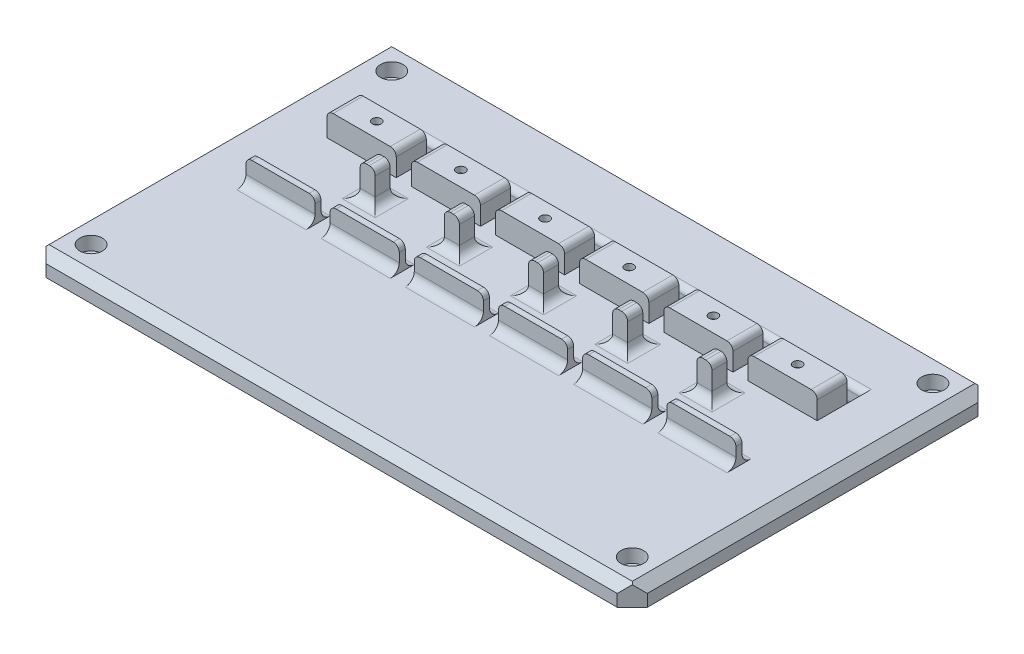
SolidWorks part; units mm, degrees
ref_plane "Front Plane" through (0, 0, 0) normal (0, 0, 1) x (1, 0, 0)
ref_plane "Top Plane" through (0, 0, 0) normal (0, 1, 0) x (1, 0, 0)
ref_plane "Right Plane" through (0, 0, 0) normal (1, 0, 0) x (0, 0, -1)
sketch "Sketch1" plane through (0, 0, 0) normal (0, 1, 0) x (1, 0, 0)
  line L1 (-111.1824, -29.2905) -> (88.8176, -29.2905)
  line L2 (-111.1824, -29.2905) -> (-111.1824, 90.7095)
  line L3 (-111.1824, 90.7095) -> (88.8176, 90.7095)
  line L4 (88.8176, -29.2905) -> (88.8176, 90.7095)
  dimension "D1" = 120
  dimension "D2" = 200
extrude "Boss-Extrude1" add sketch "Sketch1" along normal blind 7
chamfer "Chamfer1" distance 5 angle 45 4 edges at (88.8176, 3.5, 29.2905) (88.8176, 3.5, -90.7095) (-111.1824, 3.5, -90.7095) (-111.1824, 3.5, 29.2905)
sketch "Sketch14" plane through (0, 0, 0) normal (0, -1, 0) x (1, 0, 0)
  line L0 (-106.1824, 29.2905) -> (83.8176, 29.2905) construction
  line L1 (-111.1824, -85.7095) -> (-111.1824, 24.2905) construction
  line L2 (83.8176, -90.7095) -> (-106.1824, -90.7095) construction
  line L3 (88.8176, 24.2905) -> (88.8176, -85.7095) construction
  circle A0 centre (-101.1824, 19.2905) radius 1.5
  circle A1 centre (-101.1824, -80.7095) radius 1.5
  circle A2 centre (78.8176, 19.2905) radius 1.5
  circle A3 centre (78.8176, -80.7095) radius 1.5
  dimension "D1" = 3
  dimension "D4" = 3
  dimension "D5" = 3
  dimension "D8" = 3
  dimension "D2" = 10
  dimension "D3" = 10
  dimension "D6" = 10
  dimension "D7" = 10
extrude "Cut-Extrude13" cut sketch "Sketch14" against normal through all
sketch "Sketch16" plane through (0, 7, 0) normal (0, -1, 0) x (1, 0, 0)
  circle A0 centre (-101.1824, 19.2905) radius 3.75
  circle A1 centre (78.8176, 19.2905) radius 3.75
  circle A2 centre (-101.1824, -80.7095) radius 3.75
  circle A3 centre (78.8176, -80.7095) radius 3.75
  dimension "D1" = 7.5
  dimension "D2" = 7.5
  dimension "D3" = 7.5
  dimension "D4" = 7.5
extrude "Cut-Extrude14" cut sketch "Sketch16" along normal blind 4.5
sketch "Sketch17" plane through (0, 7, 0) normal (0, 1, 0) x (1, 0, 0)
  line L1 (-92.6824, 50.7095) -> (-69.6824, 50.7095)
  line L2 (-92.6824, 50.7095) -> (-92.6824, 60.7095)
  line L3 (-92.6824, 60.7095) -> (-69.6824, 60.7095)
  line L4 (-69.6824, 50.7095) -> (-69.6824, 60.7095)
  line L6 (83.8176, 90.7095) -> (-106.1824, 90.7095) construction
  line L7 (-64.6824, 60.7095) -> (-41.6824, 60.7095)
  line L8 (-64.6824, 60.7095) -> (-64.6824, 50.7095)
  line L9 (-64.6824, 50.7095) -> (-41.6824, 50.7095)
  line L10 (-41.6824, 60.7095) -> (-41.6824, 50.7095)
  line L11 (-36.6824, 60.7095) -> (-13.6824, 60.7095)
  line L12 (-36.6824, 60.7095) -> (-36.6824, 50.7095)
  line L13 (-36.6824, 50.7095) -> (-13.6824, 50.7095)
  line L14 (-13.6824, 60.7095) -> (-13.6824, 50.7095)
  line L15 (-8.6824, 60.7095) -> (14.3176, 60.7095)
  line L16 (-8.6824, 60.7095) -> (-8.6824, 50.7095)
  line L17 (-8.6824, 50.7095) -> (14.3176, 50.7095)
  line L18 (14.3176, 60.7095) -> (14.3176, 50.7095)
  line L19 (19.3176, 60.7095) -> (42.3176, 60.7095)
  line L20 (19.3176, 60.7095) -> (19.3176, 50.7095)
  line L21 (19.3176, 50.7095) -> (42.3176, 50.7095)
  line L22 (42.3176, 60.7095) -> (42.3176, 50.7095)
  line L23 (47.3176, 60.7095) -> (70.3176, 60.7095)
  line L24 (47.3176, 60.7095) -> (47.3176, 50.7095)
  line L25 (47.3176, 50.7095) -> (70.3176, 50.7095)
  line L26 (70.3176, 60.7095) -> (70.3176, 50.7095)
  line L27 (-92.6824, 25.7095) -> (-69.6824, 25.7095)
  line L28 (-92.6824, 25.7095) -> (-92.6824, 23.7095)
  line L29 (-92.6824, 23.7095) -> (-69.6824, 23.7095)
  line L30 (-69.6824, 25.7095) -> (-69.6824, 23.7095)
  line L31 (-111.1824, 85.7095) -> (-111.1824, -24.2905) construction
  line L34 (-64.6824, 25.7095) -> (-41.6824, 25.7095)
  line L35 (-64.6824, 25.7095) -> (-64.6824, 23.7095)
  line L36 (-64.6824, 23.7095) -> (-41.6824, 23.7095)
  line L37 (-41.6824, 25.7095) -> (-41.6824, 23.7095)
  line L38 (-36.6824, 25.7095) -> (-13.6824, 25.7095)
  line L39 (-36.6824, 25.7095) -> (-36.6824, 23.7095)
  line L40 (-36.6824, 23.7095) -> (-13.6824, 23.7095)
  line L41 (-13.6824, 25.7095) -> (-13.6824, 23.7095)
  line L42 (-8.6824, 25.7095) -> (14.3176, 25.7095)
  line L43 (-8.6824, 25.7095) -> (-8.6824, 23.7095)
  line L44 (-8.6824, 23.7095) -> (14.3176, 23.7095)
  line L45 (14.3176, 25.7095) -> (14.3176, 23.7095)
  line L46 (19.3176, 25.7095) -> (42.3176, 25.7095)
  line L47 (19.3176, 25.7095) -> (19.3176, 23.7095)
  line L48 (19.3176, 23.7095) -> (42.3176, 23.7095)
  line L49 (42.3176, 25.7095) -> (42.3176, 23.7095)
  line L50 (47.3176, 25.7095) -> (70.3176, 25.7095)
  line L51 (47.3176, 25.7095) -> (47.3176, 23.7095)
  line L52 (47.3176, 23.7095) -> (70.3176, 23.7095)
  line L53 (70.3176, 25.7095) -> (70.3176, 23.7095)
  point P6 (-92.6824, 55.7095)
  point P33 (-69.6824, 55.7095)
  dimension "D1" = 30
  dimension "D2" = 23
  dimension "D3" = 10
  dimension "D4" = 18.5
  dimension "D5" = 5
  dimension "D6" = 5
  dimension "D7" = 5
  dimension "D8" = 5
  dimension "D9" = 5
  dimension "D10" = 2
  dimension "D11" = 25
extrude "Boss-Extrude2" add sketch "Sketch17" along normal blind 8
fillet "Fillet1" radius 3 12 edges at (58.8176, 7, -23.7095) (30.8176, 7, -23.7095) (2.8176, 7, -23.7095) (-25.1824, 7, -23.7095) (-53.1824, 7, -23.7095) (-81.1824, 7, -23.7095) (58.8176, 7, -25.7095) (30.8176, 7, -25.7095) (2.8176, 7, -25.7095) (-25.1824, 7, -25.7095) (-53.1824, 7, -25.7095) (-81.1824, 7, -25.7095)
sketch "Sketch18" plane through (0, 7, 0) normal (0, 1, 0) x (1, 0, 0)
  line L0 (-13.6824, 50.7095) -> (-13.6824, 60.7095) construction
  line L1 (-92.6824, 60.7095) -> (-13.6824, 60.7095)
  line L2 (-92.6824, 60.7095) -> (-92.6824, 66.7095)
  line L3 (-92.6824, 66.7095) -> (-13.6824, 66.7095)
  line L4 (-13.6824, 60.7095) -> (-13.6824, 66.7095)
  line L5 (-92.6824, 60.7095) -> (-92.6824, 50.7095) construction
  line L6 (70.3176, 50.7095) -> (70.3176, 60.7095) construction
  line L7 (-8.6824, 60.7095) -> (70.3176, 60.7095)
  line L8 (-8.6824, 60.7095) -> (-8.6824, 66.7095)
  line L9 (-8.6824, 66.7095) -> (70.3176, 66.7095)
  line L10 (70.3176, 60.7095) -> (70.3176, 66.7095)
  dimension "D1" = 6
extrude "Cut-Extrude15" cut sketch "Sketch18" against normal through all
sketch "Sketch22" plane through (0, 0, 0) normal (0, 1, 0) x (1, 0, 0)
  line L0 (-69.6824, 60.7095) -> (-92.6824, 60.7095) construction
  line L1 (-92.6824, 60.7095) -> (-92.6824, 50.7095) construction
  line L2 (-64.6824, 60.7095) -> (-64.6824, 50.7095) construction
  line L3 (-41.6824, 60.7095) -> (-64.6824, 60.7095) construction
  line L4 (-36.6824, 60.7095) -> (-36.6824, 50.7095) construction
  line L5 (-13.6824, 60.7095) -> (-36.6824, 60.7095) construction
  line L6 (14.3176, 60.7095) -> (-8.6824, 60.7095) construction
  line L7 (14.3176, 50.7095) -> (14.3176, 60.7095) construction
  line L8 (19.3176, 50.7095) -> (42.3176, 50.7095) construction
  line L10 (42.3176, 50.7095) -> (42.3176, 60.7095) construction
  line L11 (47.3176, 60.7095) -> (47.3176, 50.7095) construction
  line L12 (70.3176, 60.7095) -> (47.3176, 60.7095) construction
  circle A0 centre (-81.1824, 55.7095) radius 3.1
  circle A1 centre (-53.1824, 55.7095) radius 3.1
  circle A2 centre (-25.1824, 55.7095) radius 3.5
  circle A3 centre (2.8176, 55.7095) radius 3.1
  circle A4 centre (30.8176, 55.7095) radius 3.1
  circle A5 centre (58.8176, 55.7095) radius 3.1
  point P10 (-64.6824, 55.7095)
  point P13 (-53.1824, 60.7095)
  point P34 (42.3176, 55.7095)
  dimension "D1" = 6.2
  dimension "D4" = 6.2
  dimension "D7" = 7
  dimension "D10" = 6.2
  dimension "D13" = 6.2
  dimension "D16" = 6.2
  dimension "D2" = 5
  dimension "D3" = 11.5
  dimension "D5" = 11.5
  dimension "D6" = 5
  dimension "D8" = 11.5
  dimension "D9" = 5
  dimension "D11" = 5
  dimension "D12" = 11.5
  dimension "D14" = 5
  dimension "D15" = 11.5
  dimension "D17" = 11.5
  dimension "D18" = 5
extrude "Cut-Extrude17" cut sketch "Sketch22" along normal blind 13
sketch "Sketch23" plane through (0, 13, 0) normal (0, -1, 0) x (1, 0, 0)
  circle A0 centre (-81.1824, -55.7095) radius 1.5
  circle A1 centre (-53.1824, -55.7095) radius 1.5
  circle A2 centre (-25.1824, -55.7095) radius 1.5
  circle A3 centre (2.8176, -55.7095) radius 1.5
  circle A4 centre (30.8176, -55.7095) radius 1.5
  circle A5 centre (58.8176, -55.7095) radius 1.5
extrude "Cut-Extrude18" cut sketch "Sketch23" against normal through all
sketch "Sketch24" plane through (0, 7, 0) normal (0, 1, 0) x (1, 0, 0)
  line L0 (-69.6824, 50.7095) -> (-69.6824, 60.7095) construction
  line L1 (-69.6824, 43.7095) -> (-64.6824, 43.7095)
  line L2 (-69.6824, 43.7095) -> (-69.6824, 38.7095)
  line L3 (-69.6824, 38.7095) -> (-64.6824, 38.7095)
  line L4 (-64.6824, 43.7095) -> (-64.6824, 38.7095)
  line L5 (-64.6824, 60.7095) -> (-64.6824, 50.7095) construction
  line L6 (-64.6824, 50.7095) -> (-41.6824, 50.7095) construction
  line L7 (-41.6824, 50.7095) -> (-41.6824, 60.7095) construction
  line L8 (-41.6824, 43.7095) -> (-36.6824, 43.7095)
  line L9 (-41.6824, 43.7095) -> (-41.6824, 38.7095)
  line L10 (-41.6824, 38.7095) -> (-36.6824, 38.7095)
  line L11 (-36.6824, 43.7095) -> (-36.6824, 38.7095)
  line L12 (-36.6824, 60.7095) -> (-36.6824, 50.7095) construction
  line L13 (-13.6824, 50.7095) -> (-13.6824, 60.7095) construction
  line L14 (-13.6824, 43.7095) -> (-8.6824, 43.7095)
  line L15 (-13.6824, 43.7095) -> (-13.6824, 38.7095)
  line L16 (-13.6824, 38.7095) -> (-8.6824, 38.7095)
  line L17 (-8.6824, 43.7095) -> (-8.6824, 38.7095)
  line L18 (14.3176, 43.7095) -> (19.3176, 43.7095)
  line L19 (14.3176, 43.7095) -> (14.3176, 38.7095)
  line L20 (14.3176, 38.7095) -> (19.3176, 38.7095)
  line L21 (19.3176, 43.7095) -> (19.3176, 38.7095)
  line L22 (42.3176, 43.7095) -> (47.3176, 43.7095)
  line L23 (42.3176, 43.7095) -> (42.3176, 38.7095)
  line L24 (42.3176, 38.7095) -> (47.3176, 38.7095)
  line L25 (47.3176, 43.7095) -> (47.3176, 38.7095)
  line L26 (14.3176, 50.7095) -> (14.3176, 60.7095) construction
  line L27 (42.3176, 50.7095) -> (42.3176, 60.7095) construction
  line L28 (-8.6824, 60.7095) -> (-8.6824, 50.7095) construction
  line L29 (19.3176, 60.7095) -> (19.3176, 50.7095) construction
  line L30 (47.3176, 60.7095) -> (47.3176, 50.7095) construction
  dimension "D1" = 7
  dimension "D2" = 5
extrude "Boss-Extrude3" add sketch "Sketch24" along normal blind 11
fillet "Fillet2" radius 3 10 edges at (-64.6824, 7, -41.2095) (-36.6824, 7, -41.2095) (47.3176, 7, -41.2095) (42.3176, 7, -41.2095) (19.3176, 7, -41.2095) (14.3176, 7, -41.2095) (-8.6824, 7, -41.2095) (-13.6824, 7, -41.2095) (-41.6824, 7, -41.2095) (-69.6824, 7, -41.2095)
fillet "Fillet3" radius 3 10 edges at (-39.1824, 7, -38.7095) (-67.1824, 7, -38.7095) (44.8176, 7, -43.7095) (16.8176, 7, -43.7095) (-11.1824, 7, -43.7095) (-39.1824, 7, -43.7095) (-67.1824, 7, -43.7095) (44.8176, 7, -38.7095) (16.8176, 7, -38.7095) (-11.1824, 7, -38.7095)
fillet "Fillet4" radius 2 10 edges at (47.3176, 18, -41.2095) (42.3176, 18, -41.2095) (19.3176, 18, -41.2095) (14.3176, 18, -41.2095) (-8.6824, 18, -41.2095) (-13.6824, 18, -41.2095) (-36.6824, 18, -41.2095) (-41.6824, 18, -41.2095) (-64.6824, 18, -41.2095) (-69.6824, 18, -41.2095)
fillet "Fillet5" radius 2 2 edges at (30.8176, 7, -66.7095) (-53.1824, 7, -66.7095)
fillet "Fillet6" radius 2 4 edges at (-13.6824, 0, -63.7095) (-8.6824, 0, -63.7095) (30.8176, 0, -66.7095) (-53.1824, 0, -66.7095)
fillet "Fillet7" radius 2 24 edges at (-41.6824, 15, -24.7095) (-13.6824, 15, -24.7095) (14.3176, 15, -24.7095) (42.3176, 15, -24.7095) (70.3176, 15, -24.7095) (-69.6824, 15, -24.7095) (-8.6824, 15, -24.7095) (19.3176, 15, -24.7095) (47.3176, 15, -24.7095) (-36.6824, 15, -24.7095) (-64.6824, 15, -24.7095) (-92.6824, 15, -24.7095) (70.3176, 15, -55.7095) (47.3176, 15, -55.7095) (42.3176, 15, -55.7095) (19.3176, 15, -55.7095) (-13.6824, 15, -55.7095) (-36.6824, 15, -55.7095) (-41.6824, 15, -55.7095) (-64.6824, 15, -55.7095) (-69.6824, 15, -55.7095) (-92.6824, 15, -55.7095) (14.3176, 15, -55.7095) (-8.6824, 15, -55.7095)
chamfer "Chamfer2" distance 3 angle 45 4 edges at (88.8176, 7, -30.7095) (-11.1824, 7, -90.7095) (-111.1824, 7, -30.7095) (-11.1824, 7, 29.2905)
